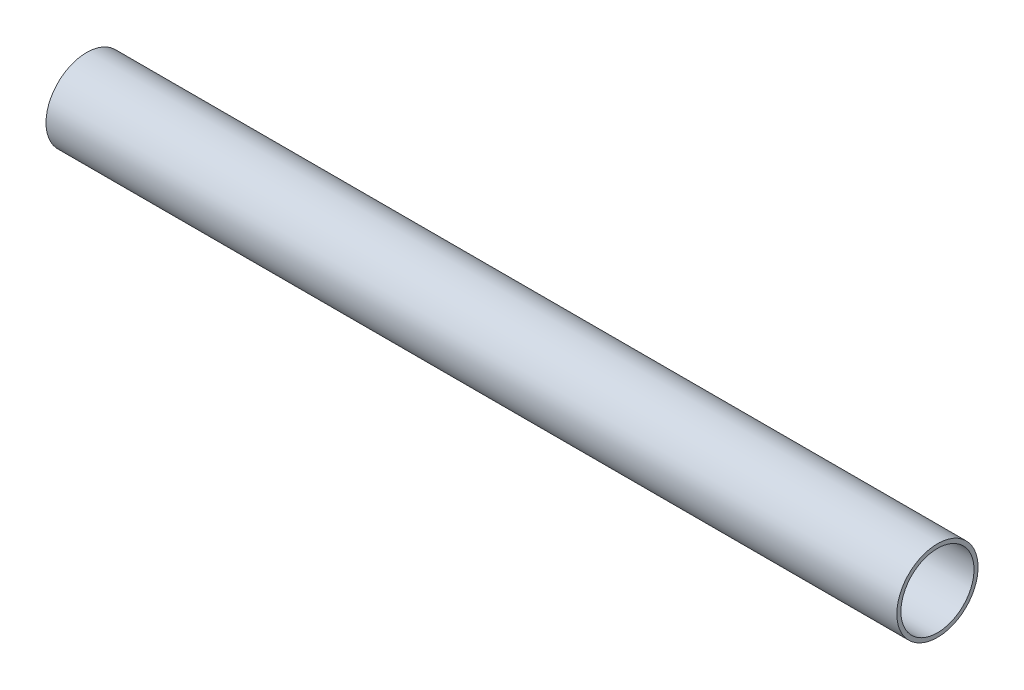
SolidWorks part; units mm, degrees
material "PC High Viscosity"
ref_plane "Front Plane" through (0, 0, 0) normal (0, 0, 1) x (1, 0, 0)
ref_plane "Top Plane" through (0, 0, 0) normal (0, 1, 0) x (1, 0, 0)
ref_plane "Right Plane" through (0, 0, 0) normal (1, 0, 0) x (0, 0, -1)
sketch "Sketch1" plane through (0, 0, 0) normal (1, 0, 0) x (0, 0, -1)
  circle A0 centre (0, 0) radius 15.875
  dimension "D1" = 31.75
extrude "Extrude-Thin1" add sketch "Sketch1" along normal mid plane 332.5813 thin thin type one direction reverse wall 1.5875
sketch "Sketch2" plane through (0, 0, 0) normal (0, 0, 1) x (1, 0, 0)
  line L0 (-166.2906, -15.875) -> (166.2906, -15.875) construction
  line L1 (104.0156, -15.875) -> (125.0156, -15.875)
  line L2 (104.0156, -15.875) -> (104.0156, 15.875)
  line L3 (104.0156, 15.875) -> (125.0156, 15.875)
  line L4 (125.0156, -15.875) -> (125.0156, 15.875)
  line L5 (166.2906, 15.875) -> (-166.2906, 15.875) construction
  line L6 (166.2906, -15.875) -> (166.2906, 15.875) construction
  line L7 (0, 0) -> (0, 11.1276) construction
  line L8 (-125.0156, -15.875) -> (-125.0156, 15.875)
  line L9 (-104.0156, 15.875) -> (-125.0156, 15.875)
  line L10 (-104.0156, -15.875) -> (-104.0156, 15.875)
  line L11 (-104.0156, -15.875) -> (-125.0156, -15.875)
  line L13 (166.2906, -15.875) -> (163.9665, -15.875)
  line L14 (166.2906, -15.875) -> (166.2906, 15.875)
  line L15 (166.2906, 15.875) -> (163.9665, 15.875)
  line L16 (163.9665, -15.875) -> (163.9665, 15.875)
  dimension "D1" = 41.275
  dimension "D2" = 21
  dimension "D3" = 2.3241
equation "\"D2@Sketch2\"=21mm"
